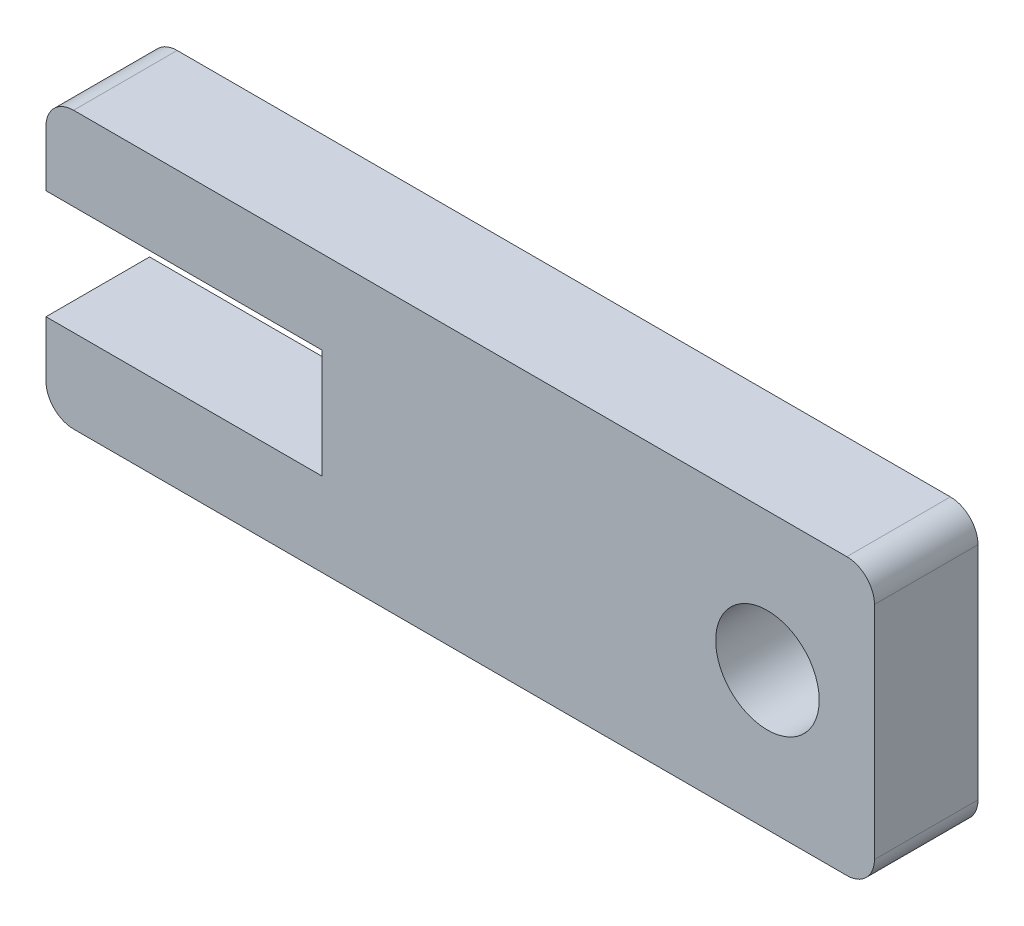
SolidWorks part; units mm, degrees
material "Corrugated Paper"
ref_plane "Front Plane" through (0, 0, 0) normal (0, 0, 1) x (1, 0, 0)
ref_plane "Top Plane" through (0, 0, 0) normal (0, 1, 0) x (1, 0, 0)
ref_plane "Right Plane" through (0, 0, 0) normal (1, 0, 0) x (0, 0, -1)
sketch "Sketch1" plane through (0, 0, 0) normal (0, 0, 1) x (1, 0, 0)
  line L0 (-12.7, 2.5082) -> (-12.7, 6.35)
  line L1 (-12.7, -2.5082) -> (0, -2.5082)
  line L3 (-12.7, 2.5082) -> (0, 2.5082)
  line L4 (0, -2.5082) -> (0, 2.5082)
  line L5 (-12.7, 6.35) -> (25.4, 6.35)
  line L6 (0, 0) -> (25.4, 0) construction
  line L7 (25.4, 6.35) -> (25.4, -6.35)
  line L8 (-12.7, -6.35) -> (25.4, -6.35)
  line L9 (-12.7, -2.5082) -> (-12.7, -6.35)
  dimension "D2" = 5.0165
  dimension "D3" = 25.4
  dimension "D4" = 12.7
extrude "Boss-Extrude1" add sketch "Sketch1" along normal mid plane 4.7625
fillet "Fillet1" radius 1.27 4 edges at (-12.7, -6.35, 0) (25.4, -6.35, 0) (25.4, 6.35, 0) (-12.7, 6.35, 0)
sketch "Sketch2" plane through (0, 0, 2.3813) normal (0, 0, 1) x (1, 0, 0)
  line L0 (0, 0) -> (25.4, 0) construction
  line L1 (25.4, -5.08) -> (25.4, 5.08) construction
  circle A0 centre (20.4787, 0) radius 2.3813
  dimension "D1" = 4.7625
  dimension "D2" = 2.54
extrude "Cut-Extrude1" cut sketch "Sketch2" against normal through all
equation "\"D2@Sketch1\"=\"thick\"+\"clear\""
equation "\"D1@Sketch2\" = \"rodThick\""
equation "\"D1@Boss-Extrude1\"= \"thick\""
equation "\"rodThick\"= 3/16in"
equation "\"thick\"= 3/16in"
equation "\"clear\"= 0.01in"
